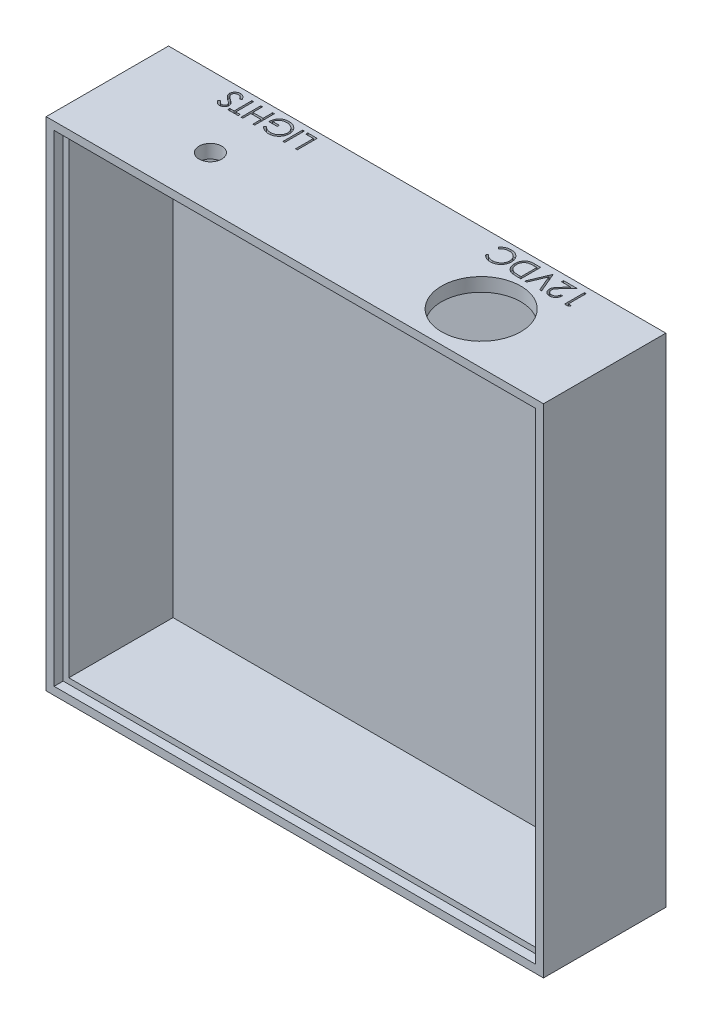
SolidWorks part; units mm, degrees
ref_plane "Front Plane" through (0, 0, 0) normal (0, 0, 1) x (1, 0, 0)
ref_plane "Top Plane" through (0, 0, 0) normal (0, 1, 0) x (1, 0, 0)
ref_plane "Right Plane" through (0, 0, 0) normal (1, 0, 0) x (0, 0, -1)
sketch "Sketch2" plane through (0, 0, 0) normal (0, 0, 1) x (1, 0, 0)
  line L0 (-2.4, -2.4) -> (85.4, -2.4)
  line L1 (0, 0) -> (83, 0)
  line L2 (0, 0) -> (0, 83)
  line L3 (0, 83) -> (83, 83)
  line L4 (83, 0) -> (83, 83)
  line L5 (85.4, -2.4) -> (85.4, 85.4)
  line L6 (-2.4, 85.4) -> (85.4, 85.4)
  line L7 (-2.4, -2.4) -> (-2.4, 85.4)
  dimension "D1" = 83
  dimension "D2" = 2.4
extrude "Boss-Extrude1-Walls" add sketch "Sketch2" along normal blind 20
extrude "Boss-Extrude2-Base" add sketch "Sketch2<3>" against normal blind 1.6 contours L7 L6 L5 L0
sketch "Sketch2<3>" plane through (0, 0, 0) normal (0, 0, 1) x (1, 0, 0) same geometry as "Sketch2"
sketch "Sketch3" plane through (0, 85.4, 0) normal (0, 1, 0) x (1, 0, 0)
  line L4 (-2.4, -20) -> (-2.4, 1.6) construction
  line L5 (85.4, -20) -> (85.4, 1.6) construction
  line L6 (85.4, -20) -> (-2.4, -20) construction
  line L7 (17.6, -11) -> (65.4, -11) construction
  circle A0 centre (17.6, -11) radius 2
  circle A1 centre (65.4, -11) radius 7
  dimension "D5" = 4
  dimension "D1" = 14
  dimension "D2" = 20
  dimension "D3" = 20
  dimension "D6" = 9
extrude "Cut-Extrude1" cut sketch "Sketch3" against normal up to next
sketch "Sketch4" plane through (0, 85.4, 0) normal (0, 1, 0) x (1, 0, 0)
  line L0 (79.2282, 0.6) -> (51.5718, 0.6) construction
  line L1 (51.5718, 0.6) -> (31.4282, 0.6) construction
  line L2 (31.4282, 0.6) -> (3.7718, 0.6) construction
  line L3 (-2.4, 1.6) -> (85.4, 1.6) construction
  text T0 "12VDC"
  text T1 "LIGHTS"
  point P4 (65.4, -11)
  point P5 (17.6, -11)
  point P6 (0, 0)
  point P7 (65.4, 0.6)
  point P10 (0, 0)
  point P11 (17.6, 0.6)
  dimension "D1" = 1
extrude "Cut-Extrude2" cut sketch "Sketch4" against normal blind 0.8
sketch "Sketch6" plane through (0, 0, 20) normal (0, 0, 1) x (1, 0, 0)
  line L9 (0, 0) -> (83, 0) construction
  line L10 (-1, 84) -> (84, 84)
  line L11 (-1, 84) -> (-1, -1)
  line L16 (-1, -1) -> (84, -1)
  line L17 (84, 84) -> (84, -1)
  line L18 (83, 0) -> (83, 83) construction
  line L19 (0, 0) -> (83, 0) construction
  point P0 (41.5, -1)
  point P3 (41.5, 0)
  point P5 (84, 41.5)
  point P11 (83, 41.5)
  dimension "D1" = 1
  dimension "D2" = 1
extrude "Cut-Extrude3" cut sketch "Sketch6" against normal blind 1.6
